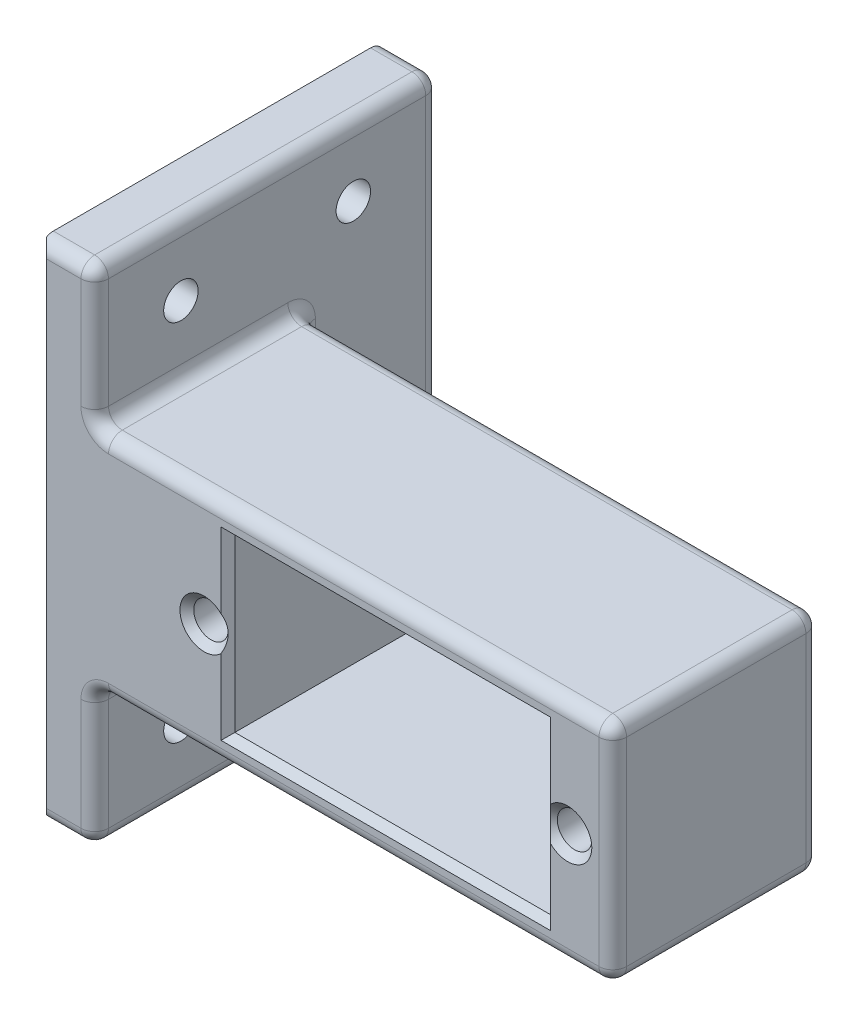
SolidWorks part; units mm, degrees
ref_plane "Front Plane" through (0, 0, 0) normal (0, 0, 1) x (1, 0, 0)
ref_plane "Top Plane" through (0, 0, 0) normal (0, 1, 0) x (1, 0, 0)
ref_plane "Right Plane" through (0, 0, 0) normal (1, 0, 0) x (0, 0, -1)
sketch "Sketch1" plane through (0, 0, 0) normal (0, 0, 1) x (1, 0, 0)
  line L0 (-25.1103, 139.7) -> (-25.1103, -139.7) construction
  line L1 (-25.1103, 139.7) -> (-25.1103, -139.7) construction
  line L2 (0, 0) -> (27.8634, 0) construction
  line L3 (11.45, 6.2) -> (-11.45, 6.2)
  line L4 (-11.25, 6) -> (-11.25, -6)
  line L5 (-11.25, -6) -> (11.25, -6)
  line L6 (11.25, -6) -> (11.25, 6)
  line L7 (11.25, 6) -> (-11.25, 6)
  line L8 (-11.25, 6) -> (-11.25, -6) construction
  line L9 (-11.25, -6) -> (11.25, -6) construction
  line L10 (11.25, -6) -> (11.25, 6) construction
  line L11 (11.25, 6) -> (-11.25, 6) construction
  line L12 (-11.45, 6.2) -> (-11.45, -6.2)
  line L13 (-11.45, -6.2) -> (11.45, -6.2)
  line L14 (11.45, -6.2) -> (11.45, 6.2)
  line L15 (16.45, -8.2) -> (16.45, 8.2)
  line L16 (16.45, 8.2) -> (-21.1103, 8.2)
  line L17 (-21.1103, 8.2) -> (-21.1103, 18.2)
  line L18 (-21.1103, 18.2) -> (-25.1103, 18.2)
  line L19 (-25.1103, 18.2) -> (-25.1103, -18.2)
  line L20 (-21.1103, -18.2) -> (-25.1103, -18.2)
  line L21 (-21.1103, -8.2) -> (-21.1103, -18.2)
  line L22 (16.45, -8.2) -> (-21.1103, -8.2)
  arc A0 (14.3256, 0.5) -> (14.3256, -0.5) centre (13.18, 0) ccw construction
  arc A1 (14.3256, 0.5) -> (14.3256, -0.5) centre (13.18, 0) ccw construction
  arc A2 (-14.3256, -0.5) -> (-14.3256, 0.5) centre (-13.18, 0) ccw construction
  arc A3 (-14.3256, -0.5) -> (-14.3256, 0.5) centre (-13.18, 0) ccw construction
  circle A4 centre (13.18, 0) radius 1.25
  circle A5 centre (-13.18, 0) radius 1.25
  point P20 (-25.1103, 0)
  point P23 (16.45, 0)
  dimension "D7" = 2.5
  dimension "D3" = 5
  dimension "D4" = 2
  dimension "D5" = 4
  dimension "D6" = 10
  dimension "D8" = 12.4
  dimension "D9" = 22.9
  dimension "D1" = 0
  dimension "D2" = 0.2
extrude "Boss-Extrude1" add sketch "Sketch1" along normal blind 15
sketch "Sketch4" plane through (-25.1103, 0, 0) normal (-1, 0, 0) x (0, 0, 1)
  line L1 (15, 18.2) -> (-10, 18.2)
  line L2 (15, 18.2) -> (15, -18.3)
  line L3 (15, -18.3) -> (-10, -18.3)
  line L4 (-10, 18.2) -> (-10, -18.3)
  dimension "D1" = 25
extrude "Boss-Extrude2" add sketch "Sketch4" against normal up to surface (4 mm away) up to face at (-21.1103, 13.2, 7.5)
sketch "Sketch3" plane through (0, 0, 0) normal (1, 0, 0) x (0, 0, -1)
  line L0 (-2.5, 18.2) -> (-2.5, 8.2) construction
  line L1 (-2.5, 8.2) -> (-2.5, 13.2) construction
  line L2 (0, 0) -> (-19.4577, 0) construction
  line L3 (-2.5, 13.2) -> (10, 13.2) construction
  line L4 (0, 8.2) -> (0, -8.2)
  line L5 (10, 18.2) -> (-15, 18.2)
  line L6 (-15, 18.2) -> (-15, 8.2)
  line L7 (-15, 8.2) -> (0, 8.2)
  line L8 (0, 8.2) -> (0, -8.2) construction
  line L9 (10, 18.2) -> (-15, 18.2) construction
  line L10 (-15, 18.2) -> (-15, 8.2) construction
  line L11 (-15, 8.2) -> (0, 8.2) construction
  line L19 (-15, -18.3) -> (10, -18.3)
  line L20 (-15, -18.3) -> (10, -18.3) construction
  line L21 (10, -18.3) -> (10, 18.2)
  line L22 (10, -18.3) -> (10, 18.2) construction
  line L23 (0, -8.2) -> (-15, -8.2)
  line L24 (0, -8.2) -> (-15, -8.2) construction
  line L25 (-15, -8.2) -> (-15, -18.3)
  line L26 (-15, -8.2) -> (-15, -18.3) construction
  circle A0 centre (-8.75, 13.2) radius 1.25
  circle A1 centre (3.75, 13.2) radius 1.25
  circle A2 centre (3.75, -13.2) radius 1.25
  circle A3 centre (-8.75, -13.2) radius 1.25
  point P8 (3.75, 13.2)
  point P21 (-4.5, 13.3)
  point P22 (0, 0)
  point P23 (-9.0251, 13.3)
  dimension "D2" = 2.5
  dimension "D1" = 0
extrude "Cut-Extrude1" cut sketch "Sketch3" against normal through all
chamfer "Chamfer1" distance 0.5 angle 45 7 edges at (-11.93, 0, 15) (14.43, 0, 15) (0, 6.2, 15) (-11.45, 0, 15) (0, -6.2, 15) (11.45, 0, 15) (-25.1103, -0.05, 15)
fillet "Fillet1" radius 1 20 edges at (-21.1103, -13.25, 15) (-21.1103, 0, 0) (-21.1103, 13.2, 15) (-21.1103, -8.2, 7.5) (-2.3302, -8.2, 15) (-2.3302, -8.2, 0) (-2.3302, 8.2, 15) (-21.1103, 8.2, 7.5) (-2.3302, 8.2, 0) (16.45, -8.2, 7.5) (16.45, 0, 15) (16.45, 8.2, 7.5) (16.45, 0, 0) (-21.1103, 18.2, 2.5) (-22.8603, 18.2, 15) (-23.1103, -18.3, -10) (-23.1103, 18.2, -10) (-21.1103, -0.05, -10) (-22.8603, -18.3, 15) (-21.1103, -18.3, 2.5)
